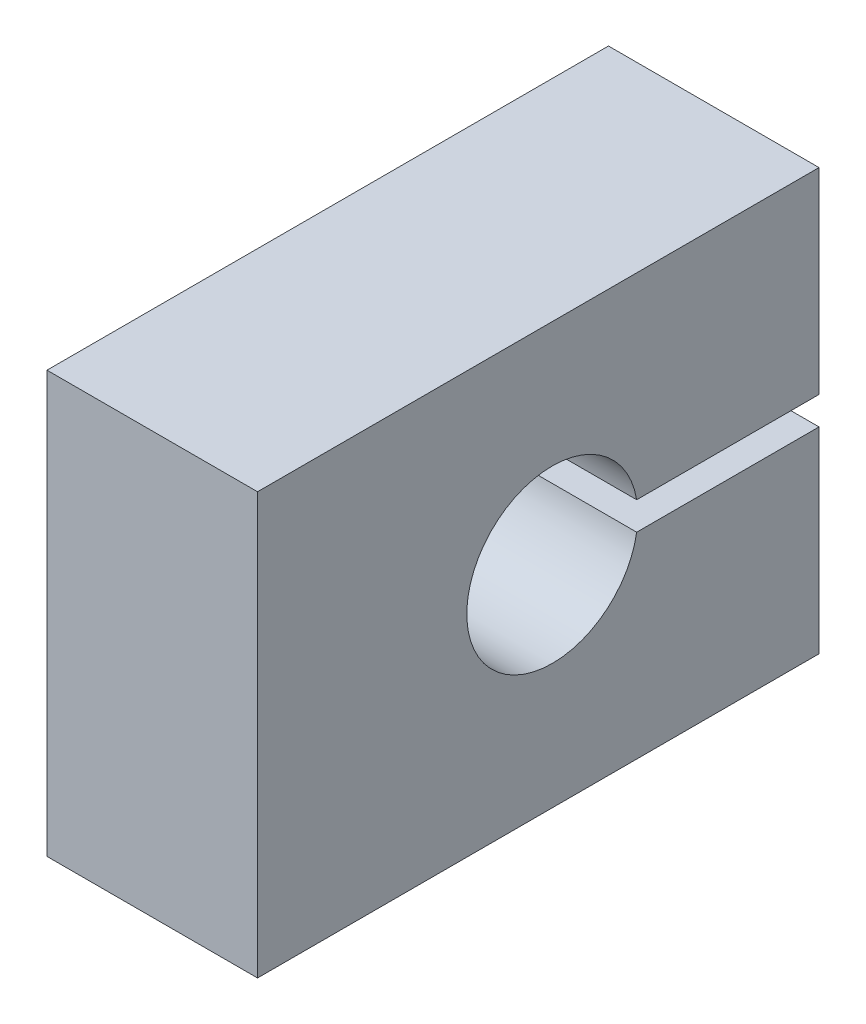
SolidWorks part; units mm, degrees
material "6061 Alloy"
ref_plane "Front Plane" through (0, 0, 0) normal (0, 0, 1) x (1, 0, 0)
ref_plane "Top Plane" through (0, 0, 0) normal (0, 1, 0) x (1, 0, 0)
ref_plane "Right Plane" through (0, 0, 0) normal (1, 0, 0) x (0, 0, -1)
sketch "Sketch2" plane through (0, 0, 0) normal (1, 0, 0) x (0, 0, -1)
  line L0 (0, 19.05) -> (26.67, 19.05) construction
  line L1 (0, 0) -> (50.8, 0)
  line L2 (0, 0) -> (0, 38.1)
  line L3 (0, 38.1) -> (50.8, 38.1)
  line L4 (50.8, 0) -> (50.8, 17.78)
  line L5 (26.67, 19.05) -> (50.8, 19.05) construction
  line L6 (34.3029, 17.78) -> (50.8, 17.78)
  line L7 (34.3029, 20.32) -> (50.8, 20.32)
  line L8 (50.8, 20.32) -> (50.8, 38.1)
  line L9 (26.67, 20.32) -> (50.8, 20.32) construction
  line L10 (26.67, 17.78) -> (50.8, 17.78) construction
  arc A0 (34.3029, 20.32) -> (34.3029, 17.78) centre (26.67, 19.05) ccw
  dimension "D4" = 15.4756
  dimension "D1" = 38.1
  dimension "D2" = 50.8
  dimension "D3" = 26.67
  dimension "D5" = 1.27
  dimension "D6" = 1.27
extrude "Boss-Extrude1" add sketch "Sketch2" along normal blind 19.05
sketch "Sketch4" plane through (0, 0, 0) normal (0, -1, 0) x (1, 0, 0)
  line L0 (9.525, 0) -> (9.525, -12.7) construction
  line L1 (19.05, 0) -> (0, 0) construction
  line L2 (9.525, -12.7) -> (9.525, -38.1) construction
  line L3 (9.525, -38.1) -> (9.525, -50.8) construction
  line L4 (19.05, -50.8) -> (0, -50.8) construction
  dimension "D1" = 25.4
hole_wizard "1/4-20 Tapped Hole1" positions "Sketch5" profile "Sketch6" tap size "1/4-20" standard "ANSI Inch"
sketch "Sketch5" plane through (0, 0, 0) normal (0, -1, 0) x (-1, 0, 0)
  point P0 (-9.525, 12.7)
  point P3 (-9.525, 38.1)
sketch "Sketch6" plane through (9.525, 0, -12.7) normal (1, 0, 0) x (0, 0, -1)
  line L0 (0, 0) -> (0, 18.0438)
  line L1 (0, 18.0438) -> (2.5527, 16.51)
  line L2 (2.5527, 16.51) -> (2.5527, 0.635)
  line L3 (2.5527, 0.635) -> (3.1877, 0)
  line L5 (3.1877, 0) -> (0, 0)
  line L6 (-2.5527, 0.635) -> (-3.1877, 0) construction
  line L10 (0, 18.0438) -> (-2.5527, 16.51) construction
  line L11 (0, -6.35) -> (0, 107.95) construction
  dimension "Tap Drill Dia." = 5.1054
  dimension "Tap Drill Depth" = 16.51
  dimension "Near C'Sink Dia." = 6.3754
  dimension "Near C'Sink Angle" = 90
  dimension "Drill Angle" = 118
cosmetic thread "Hole Thread5" parameters "D1"=12.7, "D2"=6.1054
cosmetic thread "Hole Thread6" parameters "D1"=12.7, "D2"=6.1054
sketch "Sketch9" plane through (0, 38.1, 0) normal (0, 1, 0) x (1, 0, 0)
